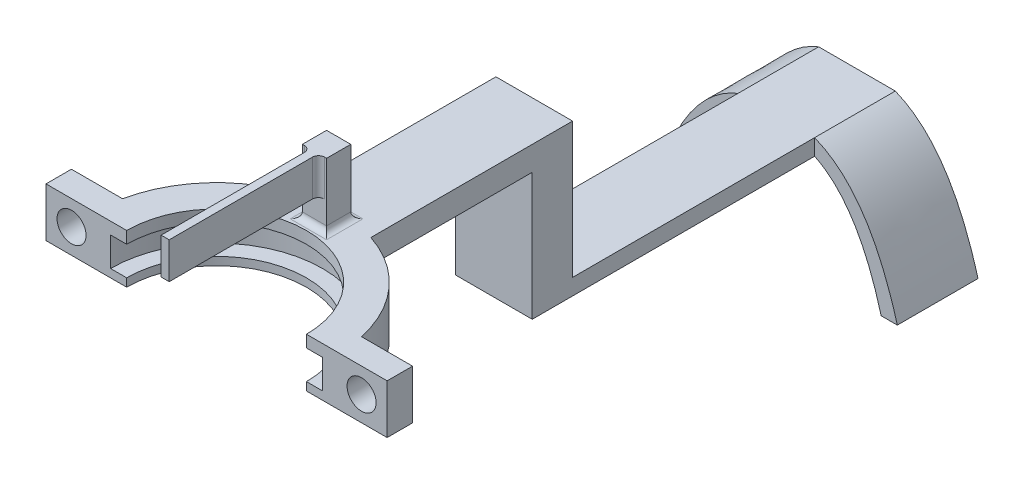
SolidWorks part; units mm, degrees
ref_plane "Front Plane" through (0, 0, 0) normal (0, 0, 1) x (1, 0, 0)
ref_plane "Top Plane" through (0, 0, 0) normal (0, 1, 0) x (1, 0, 0)
ref_plane "Right Plane" through (0, 0, 0) normal (1, 0, 0) x (0, 0, -1)
sketch "Sketch3" plane through (0, 0, 0) normal (0, 0, 1) x (1, 0, 0)
  line L2 (-62.6943, 11.7337) -> (-64.8845, 11.7337)
  line L3 (-62.8845, 10.2507) -> (-60.8845, 10.2507)
  line L5 (-60.8845, 6.6507) -> (-62.8845, 6.6507)
  line L6 (-62.8845, 6.6507) -> (-62.8845, 10.2507)
  line L10 (-64.8845, 11.7337) -> (-64.8845, 5.6398)
  line L11 (-64.8845, 5.6398) -> (-60.8845, 5.6398)
  line L12 (-60.8845, 5.6398) -> (-60.8845, 6.6507)
  line L13 (-60.8845, 10.2507) -> (-60.8845, 11.7337)
  line L14 (-60.8845, 11.7337) -> (-62.6943, 11.7337)
  dimension "D2" = 2
  dimension "D3" = 4
  dimension "D1" = 2
sketch "Sketch4" plane through (0, 0, 0) normal (0, 0, 1) x (1, 0, 0)
  line L0 (-49.7443, 0) -> (-49.7443, 12.8648) construction
  line L1 (27.6543, 0) -> (-27.6543, 0) construction
revolve "Revolve1" add sketch "Sketch3" angle 360 about L0
sketch "Sketch7" plane through (0, 11.7337, 0) normal (0, 1, 0) x (1, 0, 0)
  line L2 (-50.2443, 15.132) -> (-50.2443, 13.1308)
  line L3 (-49.2443, 15.132) -> (-49.2443, 13.1308)
  circle A0 centre (-49.7443, 0) radius 15.1403 construction
  arc A1 (-49.2443, 15.132) -> (-50.2443, 15.132) centre (-49.7443, 0) ccw
  circle A2 centre (-49.7443, 0) radius 13.1403 construction
  arc A3 (-49.2443, 13.1308) -> (-50.2443, 13.1308) centre (-49.7443, 0) ccw
  point P9 (-49.7443, 14.131)
  dimension "D1" = 1
extrude "Boss-Extrude1" add sketch "Sketch7" along normal blind 6.5
sketch "Sketch8" plane through (0, 18.2337, 0) normal (0, 1, 0) x (1, 0, 0)
  line L0 (-50.2443, 15.132) -> (-50.2443, 13.1308) construction
  line L3 (-50.2443, 15.132) -> (-50.2443, 13.1308)
  line L4 (-49.2443, 13.1308) -> (-49.2443, 15.132) construction
  line L5 (-49.2443, 13.1308) -> (-49.2443, 15.132)
  line L6 (-50.2443, 13.1308) -> (-50.2443, -6.3692)
  line L7 (-50.2443, -6.3692) -> (-49.2443, -6.3692)
  line L8 (-49.2443, -6.3692) -> (-49.2443, 13.1308)
  arc A0 (-49.2443, 15.132) -> (-50.2443, 15.132) centre (-49.7443, 0) ccw construction
  arc A1 (-49.2443, 15.132) -> (-50.2443, 15.132) centre (-49.7443, 0) ccw
  dimension "D1" = 19.5
extrude "Boss-Extrude2" add sketch "Sketch8" against normal blind 3
sketch "Sketch9" plane through (0, 11.7337, 0) normal (0, 1, 0) x (1, 0, 0)
  line L2 (-54.4943, 14.3759) -> (-54.4943, 39.3759)
  line L3 (-54.4943, 39.3759) -> (-44.9943, 39.3759)
  line L4 (-44.9943, 39.3759) -> (-44.9943, 14.3759)
  arc A0 (-50.2443, 15.132) -> (-49.2443, 15.132) centre (-49.7443, 0) ccw construction
  arc A1 (-50.2443, 15.132) -> (-54.4943, 14.3759) centre (-49.7443, 0) ccw
  arc A2 (-49.2443, 15.132) -> (-50.2443, 15.132) centre (-49.7443, 0) ccw construction
  arc A3 (-49.2443, 15.132) -> (-50.2443, 15.132) centre (-49.7443, 0) ccw
  arc A4 (-44.9943, 14.3759) -> (-49.2443, 15.132) centre (-49.7443, 0) ccw
  point P9 (-49.7443, 0)
  dimension "D1" = 25
extrude "Boss-Extrude3" add sketch "Sketch9" against normal blind 3
sketch "Sketch10" plane through (0, 8.7337, 0) normal (0, -1, 0) x (1, 0, 0)
  line L0 (-44.9943, -14.3759) -> (-44.9943, -39.3759) construction
  line L1 (-54.4943, -39.3759) -> (-44.9943, -39.3759)
  line L2 (-54.4943, -39.3759) -> (-54.4943, -34.3759)
  line L3 (-54.4943, -34.3759) -> (-44.9943, -34.3759)
  line L4 (-44.9943, -39.3759) -> (-44.9943, -34.3759)
  dimension "D1" = 5
extrude "Boss-Extrude4" add sketch "Sketch10" along normal blind 15.78
sketch "Sketch11" plane through (0, 0, -39.3759) normal (0, 0, -1) x (-1, 0, 0)
  line L0 (54.4943, -7.0463) -> (54.4943, 11.7337) construction
  line L1 (44.9943, -7.0463) -> (54.4943, -7.0463)
  line L2 (44.9943, -7.0463) -> (44.9943, -5.0463)
  line L3 (44.9943, -5.0463) -> (54.4943, -5.0463)
  line L4 (54.4943, -7.0463) -> (54.4943, -5.0463)
  dimension "D1" = 2
extrude "Boss-Extrude5" add sketch "Sketch11" along normal blind 40
sketch "Sketch13" plane through (0, 11.7337, 0) normal (0, 1, 0) x (1, 0, 0)
  line L2 (-49.7443, 3.15) -> (-49.7443, -3.15) construction
  line L3 (-28.604, 3.15) -> (-34.9353, 3.15)
  line L4 (-70.8845, 3.15) -> (-70.8845, -3.15)
  line L5 (-70.8845, -3.15) -> (-64.5532, -3.15)
  line L6 (-28.604, -3.15) -> (-28.604, 3.15)
  line L7 (-64.5532, 3.15) -> (-70.8845, 3.15)
  line L8 (-34.9353, -3.15) -> (-28.604, -3.15)
  arc A0 (-54.4943, 14.3759) -> (-44.9943, 14.3759) centre (-49.7443, 0) ccw construction
  arc A1 (-64.5532, 3.15) -> (-64.5532, -3.15) centre (-49.7443, 0) ccw
  arc A2 (-34.9353, -3.15) -> (-34.9353, 3.15) centre (-49.7443, 0) ccw
  point P10 (-49.7443, 0)
  point P13 (-49.7443, 3.15)
  dimension "D1" = 6.3
extrude "Boss-Extrude6" add sketch "Sketch13" against normal up to surface (6.0939 mm away) up to face at (-49.7443, 5.6398, -11.1403)
sketch "Sketch14" plane through (0, 0, 3.15) normal (0, 0, 1) x (1, 0, 0)
  line L0 (-70.8845, 11.7337) -> (-64.5532, 5.6398) construction
  line L1 (-28.604, 11.7337) -> (-34.9353, 5.6398) construction
  circle A0 centre (-31.7697, 8.6868) radius 1.8
  circle A1 centre (-67.7189, 8.6868) radius 1.8
  dimension "D1" = 3.6
  dimension "D2" = 3.6
extrude "Cut-Extrude1" cut sketch "Sketch14" against normal up to surface (6.3 mm away) contours A1 | A0 up to face at (-67.7189, 8.6868, -3.15)
sketch "Sketch15" plane through (0, 11.7337, 0) normal (0, 1, 0) x (1, 0, 0)
  line L0 (-70.8845, 0) -> (-23.4421, 0) construction
  line L1 (-70.8845, 3.15) -> (-70.8845, -3.15) construction
  line L2 (-7.0756, 0) -> (7.0756, 0) construction
  line L4 (-23.4421, 0) -> (-74.5953, 0)
  line L5 (-23.4421, 0) -> (-23.4421, -21.2106)
  line L6 (-23.4421, -21.2106) -> (-74.5953, -21.2106)
  line L7 (-74.5953, 0) -> (-74.5953, -21.2106)
extrude "Cut-Extrude3" cut sketch "Sketch15" against normal through all
sketch "Sketch16" plane through (0, 0, 0) normal (0, 1, 0) x (1, 0, 0)
  line L1 (-54.8883, 5.4174) -> (-45.2843, 5.4174)
  line L2 (-54.8883, 5.4174) -> (-54.8883, -6.4675)
  line L3 (-54.8883, -6.4675) -> (-45.2843, -6.4675)
  line L4 (-45.2843, 5.4174) -> (-45.2843, -6.4675)
sketch "Sketch18" plane through (0, 11.7337, 0) normal (0, 1, 0) x (1, 0, 0)
  line L0 (-50.2443, 15.132) -> (-49.2443, 15.132) construction
  line L1 (-48.2443, 15.132) -> (-51.2443, 15.132)
  line L2 (-51.2443, 15.132) -> (-51.2443, 12.132)
  line L3 (-51.2443, 12.132) -> (-48.2443, 12.132)
  line L4 (-48.2443, 12.132) -> (-48.2443, 15.132)
  point P7 (-49.7443, 15.132)
  dimension "D1" = 3
  dimension "D2" = 3
extrude "Boss-Extrude7" add sketch "Sketch18" along normal up to surface (6.5 mm away) up to face at (-49.7443, 18.2337, -4.3834)
fillet "Fillet1" radius 0.75 6 edges at (-49.7443, 11.7337, -12.132) (-48.7443, 11.7337, -15.132) (-49.7443, 11.7337, -15.1403) (-50.7443, 11.7337, -15.132) (-51.2443, 11.7337, -13.632) (-48.2443, 11.7337, -13.632)
sketch "Sketch19" plane through (0, 18.2337, 0) normal (0, 1, 0) x (1, 0, 0)
  line L18 (-50.2443, 15.132) -> (-51.2443, 15.132)
  line L19 (-51.2443, 15.132) -> (-51.2443, 12.132)
  line L20 (-51.2443, 12.132) -> (-50.2443, 12.132)
  line L21 (-50.2443, 12.132) -> (-50.2443, -6.3692)
  line L22 (-50.2443, -6.3692) -> (-49.2443, -6.3692)
  line L23 (-49.2443, -6.3692) -> (-49.2443, 12.132)
  line L24 (-49.2443, 12.132) -> (-48.2443, 12.132)
  line L25 (-48.2443, 12.132) -> (-48.2443, 15.132)
  line L26 (-48.2443, 15.132) -> (-49.2443, 15.132)
  line L27 (-50.2443, 15.132) -> (-51.2443, 15.132)
  line L28 (-51.2443, 15.132) -> (-51.2443, 12.132)
  line L29 (-51.2443, 12.132) -> (-50.2443, 12.132)
  line L30 (-50.2443, 12.132) -> (-50.2443, -6.3692)
  line L31 (-50.2443, -6.3692) -> (-49.2443, -6.3692)
  line L32 (-49.2443, -6.3692) -> (-49.2443, 12.132)
  line L33 (-49.2443, 12.132) -> (-48.2443, 12.132)
  line L34 (-48.2443, 12.132) -> (-48.2443, 15.132)
  line L35 (-48.2443, 15.132) -> (-49.2443, 15.132)
  arc A2 (-49.2443, 15.132) -> (-50.2443, 15.132) centre (-49.7443, 0) ccw
  arc A3 (-49.2443, 15.132) -> (-50.2443, 15.132) centre (-49.7443, 0) ccw
  dimension "D1" = 0
extrude "Boss-Extrude8" add sketch "Sketch19" along normal blind 1.5
fillet "Fillet2" radius 0.75 2 edges at (-49.2443, 17.4837, -12.132) (-50.2443, 17.4837, -12.132)
sketch "Sketch20" plane through (0, 0, -79.3759) normal (0, 0, -1) x (-1, 0, 0)
  line L0 (49.7443, -5.0463) -> (49.7443, -6.1882) construction
  line L1 (54.4943, -5.0463) -> (44.9943, -5.0463) construction
  line L2 (64.7443, -20.0463) -> (34.7443, -20.0463) construction
  line L4 (34.7443, -20.0463) -> (36.7443, -20.0463)
  line L5 (62.7443, -20.0463) -> (64.7443, -20.0463)
  line L8 (44.9943, -7.0463) -> (54.4943, -7.0463)
  line L9 (44.9943, -5.0463) -> (54.4943, -5.0463)
  line L11 (54.4943, -5.0463) -> (44.9943, -5.0463) construction
  line L12 (49.7443, -7.0463) -> (49.7443, -20.0463) construction
  spline S0 degree 2 poles (34.7443, -20.0463) (38.1968, -7.7468) (44.9943, -5.0463) knots 0 0 0 0.63993 0.63993 0.63993
  spline S1 degree 2 poles (36.7443, -20.0463) (39.5823, -9.6501) (44.9943, -7.0463) knots 0 0 0 0.599407 0.599407 0.599407
  spline S3 degree 2 poles (64.7443, -20.0463) (61.2918, -7.7468) (54.4943, -5.0463) knots 0 0 0 0.63993 0.63993 0.63993
  spline S4 degree 2 poles (54.4943, -7.0463) (59.9062, -9.6501) (62.7443, -20.0463) knots 0.400593 0.400593 0.400593 1 1 1
  point P7 (49.7443, -20.0463)
  dimension "D3" = 2
  dimension "D1" = 15
  dimension "D2" = 30
  dimension "D4" = 2
extrude "Boss-Extrude9" add sketch "Sketch20" against normal blind 10
